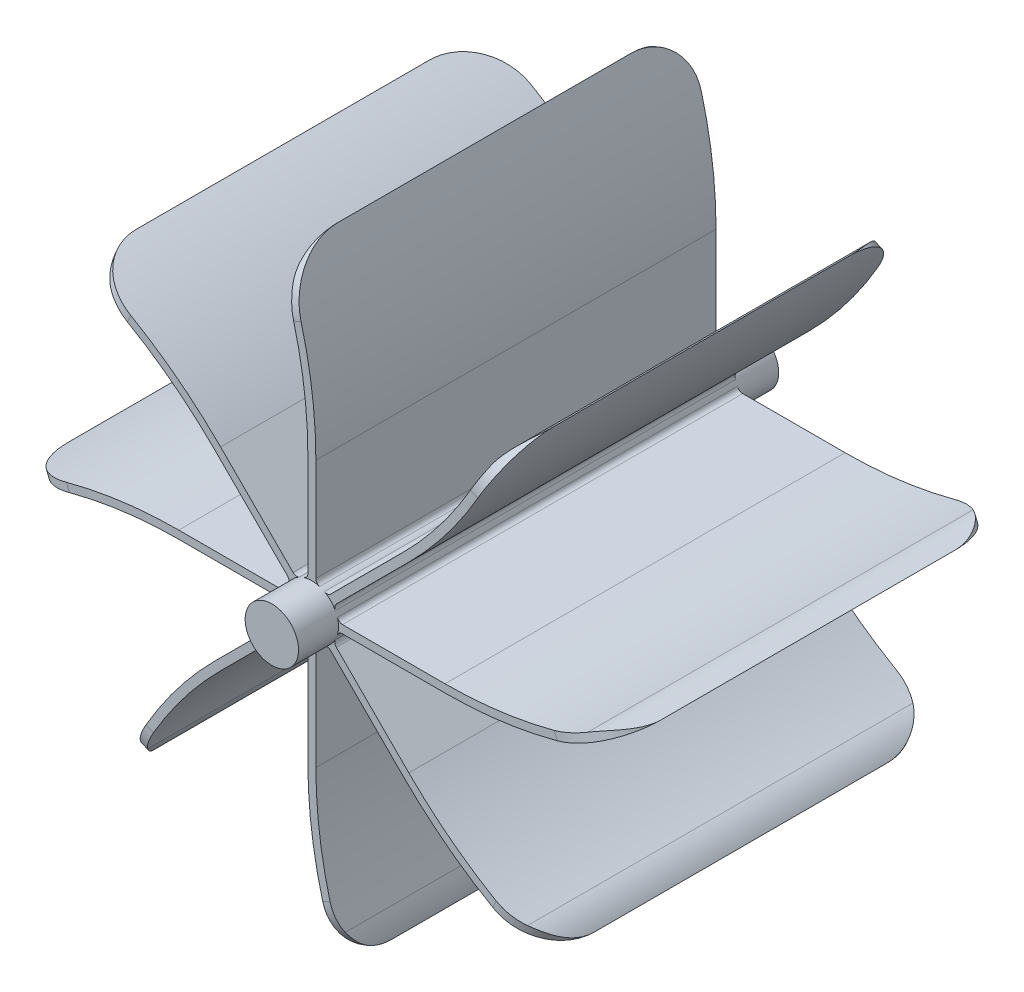
SolidWorks part; units mm, degrees
ref_plane "Front Plane" through (0, 0, 0) normal (0, 0, 1) x (1, 0, 0)
ref_plane "Top Plane" through (0, 0, 0) normal (0, 1, 0) x (1, 0, 0)
ref_plane "Right Plane" through (0, 0, 0) normal (1, 0, 0) x (0, 0, -1)
sketch "Sketch1" plane through (0, 0, 0) normal (0, 0, 1) x (1, 0, 0)
  circle A0 centre (0, 0) radius 50
  dimension "D1" = 100
extrude "Boss-Extrude1" add sketch "Sketch1" along normal mid plane 900
sketch "Sketch2" plane through (0, 0, 0) normal (0, 0, 1) x (1, 0, 0)
  line L0 (0, 0) -> (0, 60.6251) construction
  line L1 (-7.5, 49.4343) -> (7.5, 49.4343)
  line L2 (-7.5, 49.4343) -> (-7.5, 249.4343)
  line L3 (7.5, 49.4343) -> (7.5, 249.4343)
  line L4 (-51.9744, 555.0583) -> (-65.8802, 549.4343)
  circle A1 centre (0, 0) radius 50 construction
  arc A2 (-7.5, 249.4343) -> (-65.8802, 549.4343) centre (-807.5, 249.4343) ccw
  arc A3 (7.5, 249.4343) -> (-51.9744, 555.0583) centre (-807.5, 249.4343) ccw
  dimension "D4" = 800
  dimension "D1" = 15
  dimension "D2" = 7.5
  dimension "D3" = 200
  dimension "D5" = 500
  dimension "D6" = 22.02
extrude "Boss-Extrude2" add sketch "Sketch2" along normal mid plane 750
fillet "Fillet1" radius 100 2 edges at (-58.9273, 552.2463, -375) (-58.9273, 552.2463, 375)
fillet "Fillet2" radius 100 1 edges at (-65.8802, 549.4343, 0)
pattern_circular "CirPattern1" count 8 over 360 about axis through (0, 0, 0) along (0, 0, 1) of "Boss-Extrude2", "Fillet1", "Fillet2"
fillet "Fillet3" radius 10 16 edges at (7.5, 49.4343, 0) (-7.5, 49.4343, 0) (40.2586, 29.652, 0) (29.652, 40.2586, 0) (49.4343, -7.5, 0) (49.4343, 7.5, 0) (40.2586, -29.652, 0) (29.652, -40.2586, 0) (7.5, -49.4343, 0) (-7.5, -49.4343, 0) (-29.652, -40.2586, 0) (-40.2586, -29.652, 0) (-49.4343, -7.5, 0) (-49.4343, 7.5, 0) (-40.2586, 29.652, 0) (-29.652, 40.2586, 0)
